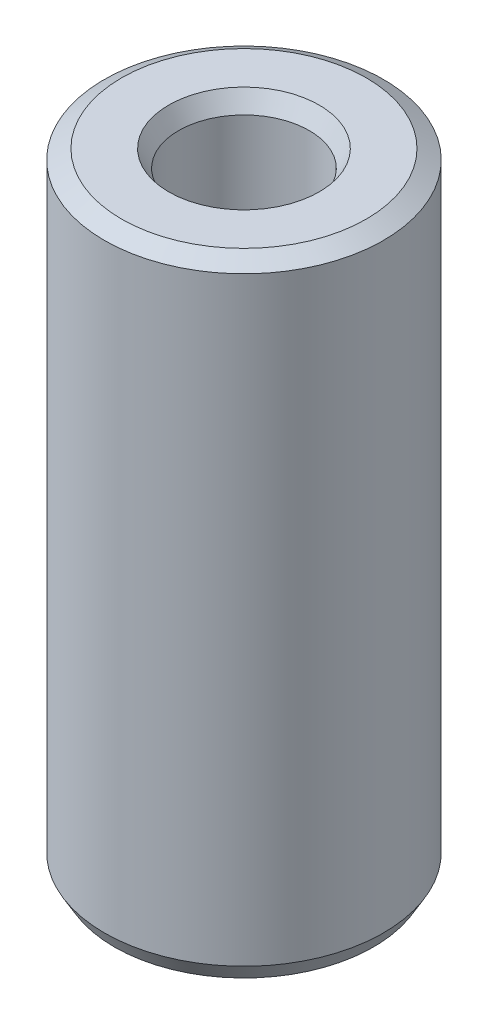
SolidWorks part; units mm, degrees
ref_plane "Front Plane" through (0, 0, 0) normal (0, 0, 1) x (1, 0, 0)
ref_plane "Top Plane" through (0, 0, 0) normal (0, 1, 0) x (1, 0, 0)
ref_plane "Right Plane" through (0, 0, 0) normal (1, 0, 0) x (0, 0, -1)
sketch "Sketch1" plane through (0, 0, 0) normal (0, 1, 0) x (1, 0, 0)
  circle A0 centre (0, 0) radius 35
  dimension "SLEEVE_OD" = 70
extrude "Boss-Extrude1" add sketch "Sketch1" along normal blind 157.2399
sketch "Sketch2" plane through (0, 0, 0) normal (0, 1, 0) x (1, 0, 0)
  circle A0 centre (0, 0) radius 16.3946
  dimension "BORE_D" = 32.7892
extrude "Cut-Extrude1" cut sketch "Sketch2" along normal through all
chamfer "Chamfer1" distance 2.4835 angle 60 4 edges at (0, 157.2399, 16.3946) (0, 0, 16.3946) (0, 0, 35) (0, 157.2399, 35) first distance on face at (0, 157.2399, 16.3946) first distance on face at (0, 0, 16.3946) first distance on face at (0, 157.2399, 35)
